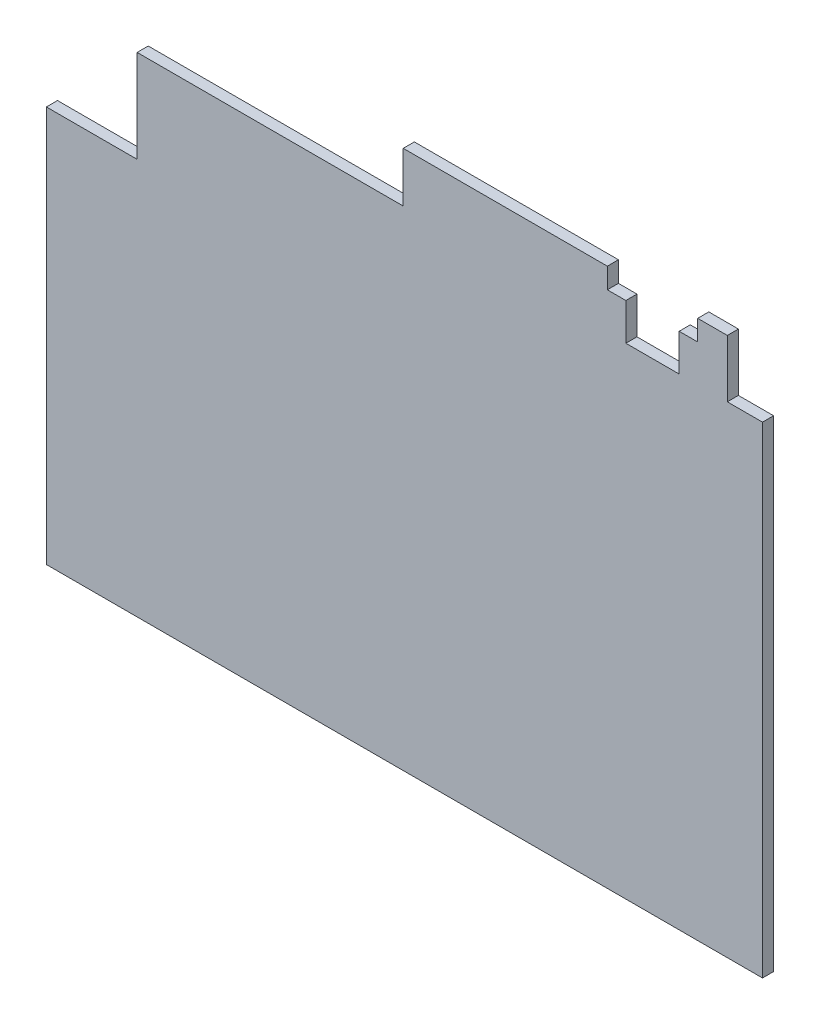
SolidWorks part; units mm, degrees
material "ABS"
ref_plane "Front Plane" through (0, 0, 0) normal (0, 0, 1) x (1, 0, 0)
ref_plane "Top Plane" through (0, 0, 0) normal (0, 1, 0) x (1, 0, 0)
ref_plane "Right Plane" through (0, 0, 0) normal (1, 0, 0) x (0, 0, -1)
sketch "Sketch1" plane through (0, 0, 0) normal (0, 0, 1) x (1, 0, 0)
  line L0 (28.5714, 236.0602) -> (28.5714, 237.0518)
  line L1 (28.5714, 277.1048) -> (28.5714, -22.8952) construction
  line L2 (28.5714, 237.0518) -> (5.4155, 237.0518)
  line L3 (5.4155, 237.0518) -> (4.5714, 268.1048)
  line L4 (4.5714, 268.1048) -> (-12.4286, 268.1048)
  line L5 (-12.4286, 268.1048) -> (-12.4286, 237.0518)
  line L6 (-12.4286, 237.0518) -> (-38.2166, 237.0518)
  line L7 (-38.2166, 237.0518) -> (-38.2166, 268.1048)
  line L8 (-221.4286, 268.1048) -> (28.5714, 268.1048) construction
  line L9 (-38.2166, 268.1048) -> (-171.4286, 268.1048)
  line L10 (-171.4286, 268.1048) -> (-171.4286, 241.1048)
  line L11 (-171.4286, 241.1048) -> (-370.1235, 241.1048)
  line L12 (-370.1235, 241.1048) -> (-370.1235, -22.8952)
  line L13 (-370.1235, -22.8952) -> (28.5714, -22.8952)
  line L14 (28.5714, -22.8952) -> (28.5714, 236.0602)
extrude "Boss-Extrude1" add sketch "Sketch1" along normal blind 6
sketch "Sketch2" plane through (0, 0, 6) normal (0, 0, 1) x (1, 0, 0)
  line L1 (-370.1235, 241.1048) -> (-315.1235, 241.1048)
  line L2 (-370.1235, 241.1048) -> (-370.1235, 191.1048)
  line L3 (-370.1235, 191.1048) -> (-315.1235, 191.1048)
  line L4 (-315.1235, 241.1048) -> (-315.1235, 191.1048)
  dimension "D1" = 55
  dimension "D2" = 50
extrude "Cut-Extrude1" cut sketch "Sketch2" against normal blind 10
sketch "Sketch3" plane through (0, 0, 6) normal (0, 0, 1) x (1, 0, 0)
  line L0 (4.5714, 268.1048) -> (-12.4286, 268.1048) construction
  line L1 (28.5714, -22.8952) -> (22.5714, -22.8952)
  line L2 (28.5714, -22.8952) -> (28.5714, 268.1048)
  line L3 (28.5714, 268.1048) -> (22.5714, 268.1048)
  line L4 (22.5714, -22.8952) -> (22.5714, 268.1048)
  line L5 (-171.4286, 241.1048) -> (-315.1235, 241.1048) construction
  line L6 (-370.1235, -22.8952) -> (-364.1235, -22.8952)
  line L7 (-370.1235, -22.8952) -> (-370.1235, 241.1048)
  line L8 (-370.1235, 241.1048) -> (-364.1235, 241.1048)
  line L9 (-364.1235, -22.8952) -> (-364.1235, 241.1048)
  dimension "D1" = 6
  dimension "D2" = 6
extrude "Cut-Extrude2" cut sketch "Sketch3" against normal blind 10
sketch "Sketch4" plane through (0, 0, 6) normal (0, 0, 1) x (1, 0, 0)
  line L1 (-38.2166, 268.1048) -> (-61.2166, 268.1048)
  line L2 (-38.2166, 268.1048) -> (-38.2166, 237.0518)
  line L3 (-38.2166, 237.0518) -> (-61.2166, 237.0518)
  line L4 (-61.2166, 268.1048) -> (-61.2166, 237.0518)
  line L5 (4.5714, 268.1048) -> (3.5714, 268.1048)
  line L6 (4.5714, 268.1048) -> (4.5714, 237.0518)
  line L7 (4.5714, 237.0518) -> (3.5714, 237.0518)
  line L8 (3.5714, 268.1048) -> (3.5714, 237.0518)
  dimension "D1" = 23
  dimension "D2" = 1
extrude "Cut-Extrude3" cut sketch "Sketch4" against normal blind 10
sketch "Sketch5" plane through (0, 0, 6) normal (0, 0, 1) x (1, 0, 0)
  line L1 (-61.2166, 237.0518) -> (-51.2166, 237.0518)
  line L2 (-61.2166, 237.0518) -> (-61.2166, 257.0518)
  line L3 (-61.2166, 257.0518) -> (-51.2166, 257.0518)
  line L4 (-51.2166, 237.0518) -> (-51.2166, 257.0518)
  line L5 (-12.4286, 237.0518) -> (-22.4286, 237.0518)
  line L6 (-12.4286, 237.0518) -> (-12.4286, 257.0518)
  line L7 (-12.4286, 257.0518) -> (-22.4286, 257.0518)
  line L8 (-22.4286, 237.0518) -> (-22.4286, 257.0518)
  dimension "D1" = 20
  dimension "D2" = 20
  dimension "D3" = 10
  dimension "D4" = 10
extrude "Boss-Extrude2" add sketch "Sketch5" against normal up to vertex (6 mm away) up to point (-61.2166, 268.1048, 0)
sketch "Sketch6" plane through (0, 0, 6) normal (0, 0, 1) x (1, 0, 0)
  line L1 (4.5714, 237.0518) -> (9.0632, 237.0518)
  line L2 (4.5714, 237.0518) -> (4.5714, 268.9907)
  line L3 (4.5714, 268.9907) -> (9.0632, 268.9907)
  line L4 (9.0632, 237.0518) -> (9.0632, 268.9907)
extrude "Cut-Extrude4" cut sketch "Sketch6" against normal blind 10
